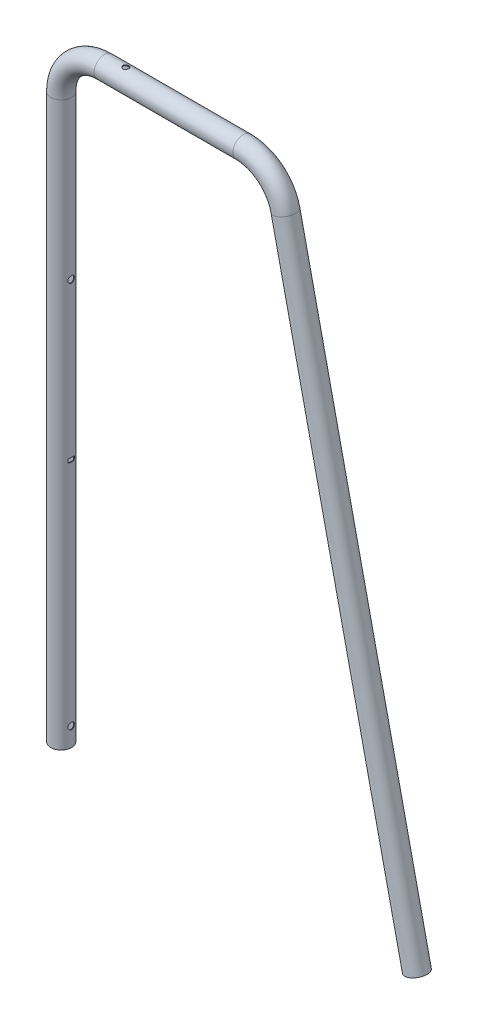
SolidWorks part; units mm, degrees
ref_plane "Front Plane" through (0, 0, 0) normal (0, 0, 1) x (1, 0, 0)
ref_plane "Top Plane" through (0, 0, 0) normal (0, 1, 0) x (1, 0, 0)
ref_plane "Right Plane" through (0, 0, 0) normal (1, 0, 0) x (0, 0, -1)
sketch "Sketch1" plane through (0, 0, 0) normal (0, 0, 1) x (1, 0, 0)
  line L0 (-85, 0) -> (85, 0)
  line L1 (-138, -53) -> (-138, -743)
  line L2 (136.7437, -41.5287) -> (297.9303, -768.5947)
  arc A0 (85, 0) -> (136.7437, -41.5287) centre (85, -53) cw
  arc A1 (-85, 0) -> (-138, -53) centre (-85, -53) ccw
  point P4 (0, 0)
  point P9 (127.537, 0)
  point P12 (-138, 0)
  dimension "D4" = 53
  dimension "D1" = 170
  dimension "D2" = 743
  dimension "D3" = 12.5
ref_plane "Plane4" through (-138, -743, 0) normal (0, -1, 0) x (-1, 0, 0)
sketch "Sketch2" plane through (-138, -743, 0) normal (0, -1, 0) x (-1, 0, 0)
  circle A0 centre (0, 0) radius 12.7
  circle A1 centre (0, 0) radius 11.9
  dimension "D1" = 0.8
sweep "Sweep1" add profiles "Sketch2" path "Sketch1"
sketch "Sketch4" plane through (0, -743, 0) normal (0, -1, 0) x (1, 0, 0)
  line L0 (-138, 12.7) -> (-138, 0) construction
  line L1 (-138, 0) -> (-150.7, 0) construction
  circle A0 centre (-138, 0) radius 12.7 construction
  circle A1 centre (-138, 0) radius 12.7 construction
ref_plane "Plane5" through (-138, -743, 0) normal (-1, 0, 0) x (0, 0, 1)
sketch "Sketch5" plane through (-138, -743, 0) normal (-1, 0, 0) x (0, 0, 1)
  line L0 (0, 0) -> (0, 23) construction
  line L1 (12.7, 0) -> (0, 0) construction
  line L2 (0, 23) -> (0, 497) construction
  circle A0 centre (0, 23) radius 4
  circle A1 centre (0, 497) radius 4
  dimension "D1" = 23
  dimension "D2" = 474
extrude "Cut-Extrude1" cut sketch "Sketch5" along normal through all and the other way up to next
sketch "Sketch6" plane through (-138, -743, 0) normal (-1, 0, 0) x (0, 0, 1)
  line L0 (0, 0) -> (0, 305.6265) construction
  line L1 (12.7, 0) -> (0, 0) construction
  line L3 (-2.5, 303.1265) -> (2.5, 303.1265)
  line L4 (-4, 304.6265) -> (-4, 306.6265)
  line L5 (-2.5, 308.1265) -> (2.5, 308.1265)
  line L6 (4, 304.6265) -> (4, 306.6265)
  line L7 (-4, 303.1265) -> (4, 308.1265) construction
  line L8 (-4, 308.1265) -> (4, 303.1265) construction
  arc A0 (4, 306.6265) -> (2.5, 308.1265) centre (2.5, 306.6265) ccw
  arc A1 (4, 304.6265) -> (2.5, 303.1265) centre (2.5, 304.6265) cw
  arc A2 (-4, 304.6265) -> (-2.5, 303.1265) centre (-2.5, 304.6265) ccw
  arc A3 (-2.5, 308.1265) -> (-4, 306.6265) centre (-2.5, 306.6265) ccw
  dimension "D3" = 1.5
  dimension "D1" = 5
  dimension "D2" = 8
extrude "Cut-Extrude2" cut sketch "Sketch6" against normal up to next and the other way up to next
sketch "Sketch7" plane through (176.368, -795.5445, 0) normal (0.2164, -0.9763, 0) x (0.9763, 0.2164, 0)
  line L0 (124.5139, 12.7) -> (124.5139, 0) construction
  line L1 (124.5139, 0) -> (137.2139, 0) construction
  circle A0 centre (124.5139, 0) radius 12.7 construction
ref_plane "Plane6" through (297.9303, -768.5947, 0) normal (0.9763, 0.2164, 0) x (0, 0, -1)
sketch "Sketch9" plane through (297.9303, -768.5947, 0) normal (0.9763, 0.2164, 0) x (0, 0, -1)
  line L0 (-12.7, 0) -> (0, 0) construction
  circle A0 centre (0, 23) radius 5.2
  dimension "D1" = 23
extrude "Cut-Extrude3" cut sketch "Sketch9" against normal up to next
sketch "Sketch11" plane through (0, 0, 0) normal (0, 1, 0) x (1, 0, 0)
  line L0 (-150.7, 0) -> (-58.7, 0) construction
  circle A0 centre (-58.7, 0) radius 3.5
  dimension "D1" = 92
extrude "Cut-Extrude4" cut sketch "Sketch11" against normal blind 50 and the other way blind 50
